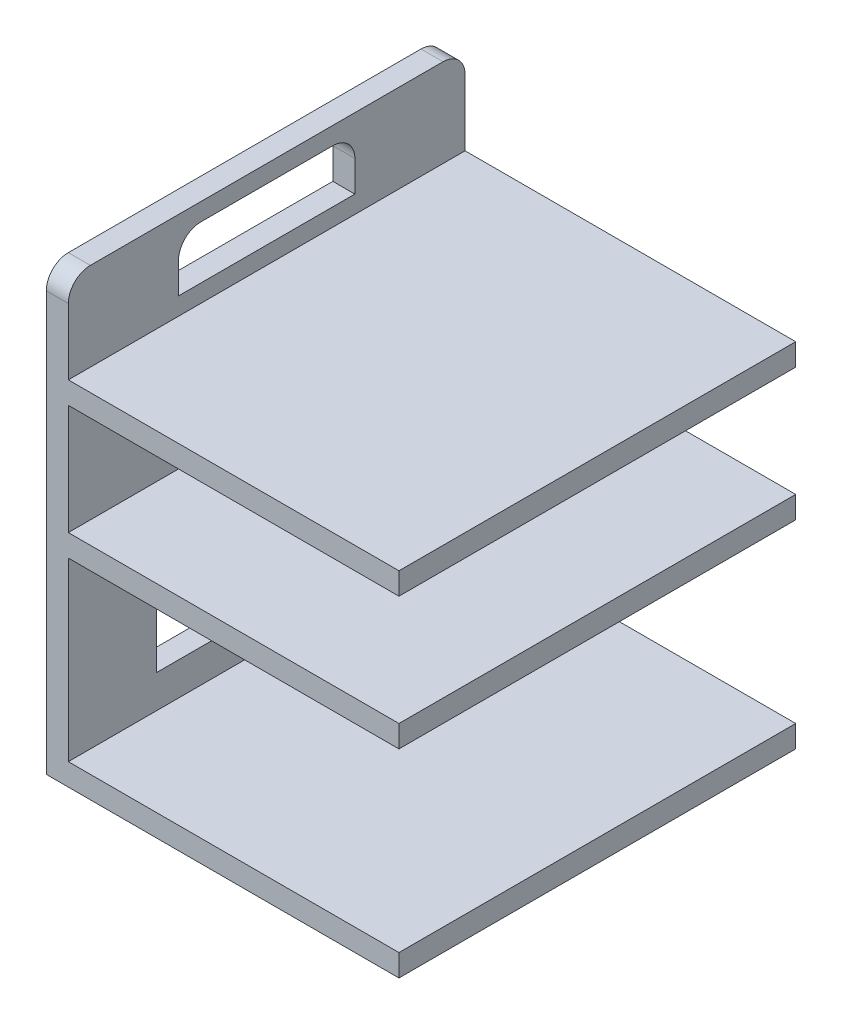
SolidWorks part; units mm, degrees
ref_plane "Front Plane" through (0, 0, 0) normal (0, 0, 1) x (1, 0, 0)
ref_plane "Top Plane" through (0, 0, 0) normal (0, 1, 0) x (1, 0, 0)
ref_plane "Right Plane" through (0, 0, 0) normal (1, 0, 0) x (0, 0, -1)
sketch "Sketch1" plane through (0, 0, 0) normal (1, 0, 0) x (0, 0, -1)
  line L0 (0, 45) -> (0, -55)
  line L1 (0, 45) -> (90, 45)
  line L2 (90, 45) -> (90, -55)
  line L3 (90, -55) -> (0, -55)
  line L4 (0, 45) -> (0, 25)
  line L5 (0, 25) -> (0, 4.7475)
  line L6 (0, 45) -> (90, 45)
  line L7 (0, 45) -> (0, 25)
  line L9 (90, 45) -> (90, 25)
  line L13 (0, 25) -> (0, 16.4414)
  line L15 (90, 25) -> (90, 16.4414)
  line L17 (0, 20) -> (0, 0)
  line L18 (0, -55) -> (0, -50)
  line L20 (0, -50) -> (0, -10)
  line L23 (0, -5) -> (0, -10)
  line L25 (90, -5) -> (90, -10)
  dimension "D1" = 100
  dimension "D2" = 90
  dimension "D3" = 20
  dimension "D4" = 20
  dimension "D6" = 5
  dimension "D7" = 40
extrude "Boss-Extrude1" add sketch "Sketch1" along normal blind 5 contours L3 L2 L1 L0 L13 L5 region at (0, -5, -45)
sketch "Sketch2" plane through (5, 0, 0) normal (1, 0, 0) x (0, 0, -1)
  line L0 (0, 45) -> (0, 25)
  line L1 (0, 45) -> (0, -55) construction
  line L2 (90, 45) -> (90, -55) construction
  line L3 (0, 25) -> (90, 25)
  line L4 (0, 25) -> (0, 20)
  line L5 (0, 20) -> (90, 20)
  line L6 (90, 25) -> (90, 20)
  line L7 (0, -50) -> (0, -10)
  line L8 (90, -55) -> (0, -55)
  line L9 (90, -55) -> (90, -50)
  line L10 (90, -50) -> (0, -50)
  line L11 (0, -55) -> (0, -50)
  line L13 (0, -10) -> (90, -10)
  line L14 (0, -10) -> (0, -5)
  line L15 (0, -5) -> (90, -5)
  line L16 (90, -10) -> (90, -5)
  line M15 (0, -55) -> (90, -55)
  line M16 (90, -55) -> (90, 45)
  line M18 (0, 45) -> (0, -55)
  dimension "D1" = 20
  dimension "D2" = 5
  dimension "D3" = 5
  dimension "D4" = 40
  dimension "D5" = 5
extrude "Boss-Extrude2" add sketch "Sketch2" along normal blind 75 contours L5 L3 M18 M16 | L15 L13 M18 M16 | L10 M16 M18 M15 region at (5, 22.5, -45) region at (5, -7.5, -45) region at (5, -52.5, -45)
sketch "Sketch4" plane through (5, 0, 0) normal (1, 0, 0) x (0, 0, -1)
  line L0 (45, 45) -> (45, 25)
  line L1 (0, 45) -> (90, 45) construction
  line L2 (0, 25) -> (90, 25) construction
  line L4 (25, 41) -> (65, 41)
  line L5 (25, 41) -> (25, 29)
  line L6 (25, 29) -> (65, 29)
  line L7 (65, 41) -> (65, 29)
  line L8 (25, 41) -> (65, 29) construction
  line L9 (25, 29) -> (65, 41) construction
  point P6 (45, 35)
  dimension "D1" = 12
  dimension "D2" = 40
extrude "Cut-Extrude1" cut sketch "Sketch4" against normal up to next contours L5 L6 L0 L4 | L7 L4 L0 L6 region at (5, 35, -55) region at (5, 35, -35)
sketch "Sketch5" plane through (5, 0, 0) normal (1, 0, 0) x (0, 0, -1)
  line L0 (45, 20) -> (45, -5)
  line L1 (0, 20) -> (90, 20) construction
  line L2 (0, -5) -> (90, -5) construction
  line L8 (25, 13.5) -> (65, 13.5)
  line L9 (25, 13.5) -> (25, 1.5)
  line L10 (25, 1.5) -> (65, 1.5)
  line L11 (65, 13.5) -> (65, 1.5)
  line L12 (25, 13.5) -> (65, 1.5) construction
  line L13 (25, 1.5) -> (65, 13.5) construction
  point P6 (45, 7.5)
  point P7 (45, 7.5)
  dimension "D1" = 12
  dimension "D2" = 40
extrude "Cut-Extrude2" cut sketch "Sketch5" against normal up to next contours L9 L10 L0 L8 | L11 L8 L0 L10 region at (5, 7.5, -55) region at (5, 7.5, -35)
sketch "Sketch7" plane through (5, 0, 0) normal (1, 0, 0) x (0, 0, -1)
  line L0 (45, -10) -> (45, -50)
  line L1 (0, -10) -> (90, -10) construction
  line L2 (90, -50) -> (0, -50) construction
  line L4 (20, -17.5) -> (70, -17.5)
  line L5 (20, -17.5) -> (20, -42.5)
  line L6 (20, -42.5) -> (70, -42.5)
  line L7 (70, -17.5) -> (70, -42.5)
  line L8 (20, -17.5) -> (70, -42.5) construction
  line L9 (20, -42.5) -> (70, -17.5) construction
  point P6 (45, -30)
  dimension "D1" = 25
  dimension "D2" = 50
extrude "Cut-Extrude3" cut sketch "Sketch7" against normal up to next contours L5 L6 L0 L4 | L7 L4 L0 L6 region at (5, -30, -57.5) region at (5, -30, -32.5)
fillet "Fillet1" radius 5 4 edges at (2.5, 41, -65) (2.5, 41, -25) (2.5, 45, -90) (2.5, 45, 0)
fillet "Fillet2" radius 5 4 edges at (2.5, -17.5, -20) (2.5, -17.5, -70) (2.5, 13.5, -25) (2.5, 13.5, -65)
